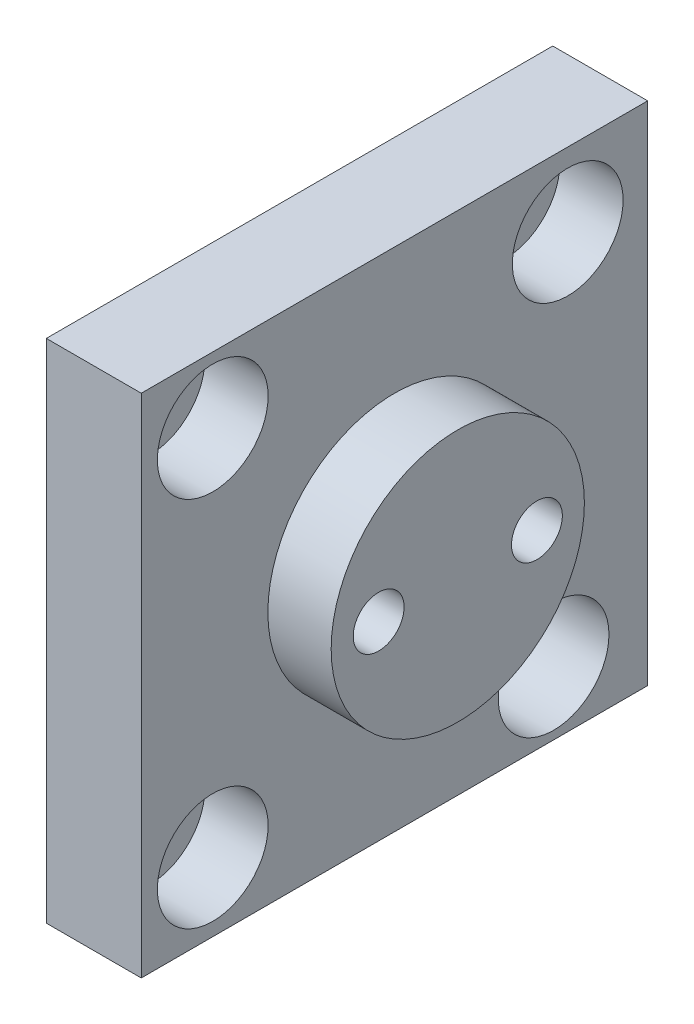
SolidWorks part; units mm, degrees
material "6061-T6 (SS)"
ref_plane "Front" through (0, 0, 0) normal (0, 0, 1) x (1, 0, 0)
ref_plane "Top" through (0, 0, 0) normal (0, 1, 0) x (1, 0, 0)
ref_plane "Right" through (0, 0, 0) normal (1, 0, 0) x (0, 0, -1)
sketch "Sketch1" plane through (0, 0, 0) normal (1, 0, 0) x (0, 0, -1)
  line L14 (-25.4, 25.4) -> (25.4, 25.4)
  line L15 (-25.4, 25.4) -> (-25.4, -25.4)
  line L16 (-25.4, -25.4) -> (25.4, -25.4)
  line L17 (25.4, 25.4) -> (25.4, -25.4)
  line L18 (-25.4, 25.4) -> (25.4, -25.4) construction
  line L19 (-25.4, -25.4) -> (25.4, 25.4) construction
  point P1 (0, 0)
  dimension "D1" = 50.8
  dimension "D2" = 50.8
extrude "Boss-Extrude1" add sketch "Sketch1" along normal blind 9.525
sketch "Sketch2" plane through (9.525, 0, 0) normal (1, 0, 0) x (0, 0, -1)
  circle A0 centre (0, 0) radius 12.7
  dimension "D1" = 25.4
extrude "Boss-Extrude2" add sketch "Sketch2" along normal blind 6.35
hole_wizard "1/4-20 Tapped Hole1" positions "Sketch3" profile "Sketch4" tap size "1/4-20" standard "ANSI Inch" end condition through all
sketch "Sketch3" plane through (15.875, 0, 0) normal (1, 0, 0) x (0, 0, -1)
  line L0 (0, 0) -> (0, -5.155) construction
  point P0 (-7.9375, 0)
  point P2 (7.9375, 0)
  dimension "D1" = 15.875
cosmetic thread "Hole Thread1" parameters "D2"=6.35
cosmetic thread "Hole Thread2" parameters "D2"=6.35
sketch "Sketch4" plane through (15.875, 0, 7.9375) normal (0, 1, 0) x (0, 0, -1)
  line L0 (0, 0) -> (0, 15.875)
  line L1 (0, 15.875) -> (2.5527, 15.875)
  line L2 (2.5527, 15.875) -> (2.5527, 0)
  line L5 (2.5527, 0) -> (0, 0)
  line L11 (0, -6.35) -> (0, 107.95) construction
  dimension "Thru Tap Drill Dia." = 5.1054
  dimension "Thru Tap Drill Depth" = 15.875
hole_wizard "CBORE for 1/4 Socket Head Cap Screw1" positions "Sketch6" profile "Sketch7" counterbore size "1/4" standard "ANSI Inch" end condition through all
sketch "Sketch6" plane through (9.525, 0, 0) normal (1, 0, 0) x (0, 0, -1)
  point P0 (-18.2292, 18.7966)
  point P2 (17.378, 18.0164)
  point P4 (15.9594, -19.0094)
  point P6 (-18.2292, -18.5129)
sketch "Sketch7" plane through (9.525, 18.7966, 18.2292) normal (0, 1, 0) x (0, 0, -1)
  line L0 (0, 0) -> (0, 9.525)
  line L1 (0, 9.525) -> (3.3782, 9.525)
  line L3 (3.3782, 9.525) -> (3.3782, 6.35)
  line L4 (3.3782, 6.35) -> (5.5562, 6.35)
  line L5 (5.5562, 6.35) -> (5.5562, 0)
  line L7 (5.5562, 0) -> (0, 0)
  line L11 (0, -6.35) -> (0, 107.95) construction
  dimension "Thru Hole Dia." = 6.7564
  dimension "Thru Hole Depth" = 9.525
  dimension "C'Bore Dia." = 11.1125
  dimension "C'Bore Depth" = 6.35
